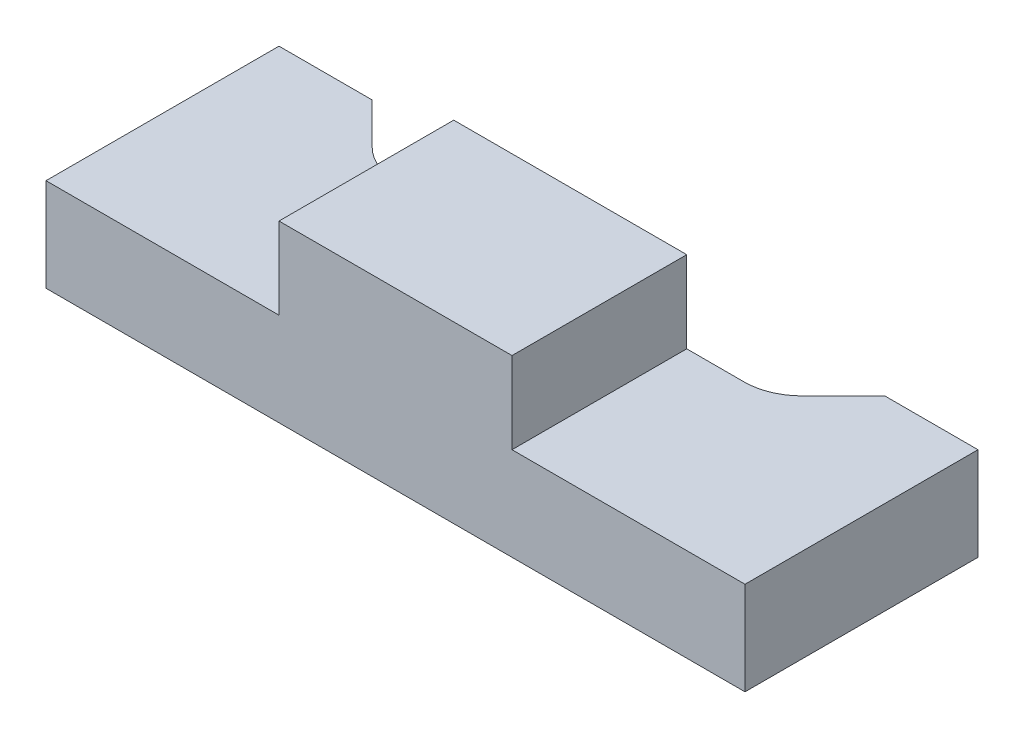
SolidWorks part; units mm, degrees
material "1060 Alloy"
ref_plane "Front Plane" through (0, 0, 0) normal (0, 0, 1) x (1, 0, 0)
ref_plane "Top Plane" through (0, 0, 0) normal (0, 1, 0) x (1, 0, 0)
ref_plane "Right Plane" through (0, 0, 0) normal (1, 0, 0) x (0, 0, -1)
sketch "Sketch4" plane through (0, 0, 0) normal (0, 0, 1) x (1, 0, 0)
  line L0 (-30, 0) -> (30, 0)
  line L1 (30, 0) -> (30, 8)
  line L2 (30, 8) -> (10, 8)
  line L3 (10, 8) -> (10, 15)
  line L4 (10, 15) -> (-10, 15)
  line L5 (-10, 15) -> (-10, 8)
  line L6 (-10, 8) -> (-30, 8)
  line L7 (-30, 8) -> (-30, 0)
  dimension "D1" = 8
  dimension "D2" = 60
  dimension "D3" = 20
  dimension "D4" = 15
extrude "Boss-Extrude2" add sketch "Sketch4" along normal blind 20
hole_wizard "Tap Drill for M10 Tap1" positions "Sketch6" profile "Sketch5" hole size "M10" standard "ISO"
sketch "Sketch6" plane through (0, 0, 0) normal (0, 0, -1) x (-1, 0, 0)
  line L0 (-10, 15) -> (10, 15) construction
  point P0 (0, 9)
  dimension "D1" = 6
sketch "Sketch5" plane through (0, 9, 0) normal (1, 0, 0) x (0, 1, 0)
  line L0 (0, 0) -> (0, 18.5537)
  line L1 (0, 18.5537) -> (4.25, 16)
  line L2 (4.25, 16) -> (4.25, 0)
  line L5 (4.25, 0) -> (0, 0)
  line L10 (0, 18.5537) -> (-4.25, 16) construction
  line L11 (0, -6.35) -> (0, 107.95) construction
  dimension "Hole Dia." = 8.5
  dimension "Hole Depth" = 16
  dimension "Drill Angle" = 118
sketch "Sketch7" plane through (0, 15, 0) normal (0, 1, 0) x (1, 0, 0)
  line L0 (-10, 0) -> (-30, 0) construction
  line L1 (-22, 0) -> (22, 0)
  line L2 (-22, 0) -> (-17, -5)
  line L3 (-17, -5) -> (17, -5)
  line L4 (22, 0) -> (17, -5)
  line L5 (30, 0) -> (10, 0) construction
  dimension "D1" = 45
  dimension "D2" = 45
  dimension "D3" = 34
  dimension "D4" = 17
  dimension "D5" = 5
extrude "Cut-Extrude1" cut sketch "Sketch7" against normal up to next
fillet "Fillet1" radius 5 2 edges at (-17, 4, 5) (17, 4, 5)
